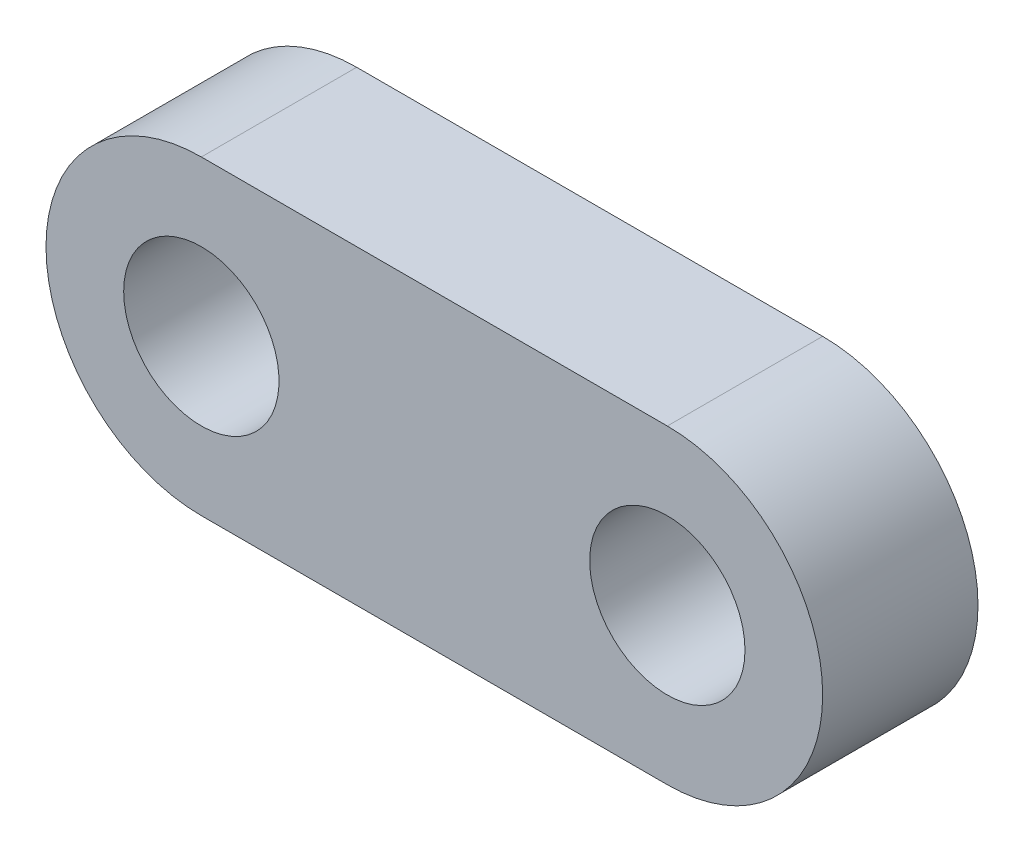
SolidWorks part; units mm, degrees
ref_plane "Front Plane" through (0, 0, 0) normal (0, 0, 1) x (1, 0, 0)
ref_plane "Top Plane" through (0, 0, 0) normal (0, 1, 0) x (1, 0, 0)
ref_plane "Right Plane" through (0, 0, 0) normal (1, 0, 0) x (0, 0, -1)
ref_plane "Plane4"
sketch "Sketch1" plane through (0, 0, 0) normal (0, 0, 1) x (1, 0, 0)
  line L0 (19.05, 0) -> (0, 0)
  line L2 (0, 12.7) -> (19.05, 12.7)
  arc A1 (0, 12.7) -> (0, 0) centre (0, 6.35) ccw
  circle A2 centre (0, 6.35) radius 3.175
  circle A3 centre (19.05, 6.35) radius 3.175
  circle A4 centre (19.05, 6.35) radius 6.35
  dimension "D1" = 19.05
extrude "Extrusion2" add sketch "Sketch1" along normal blind 6.35 contours A1 A3 A2 region at (5.2212, 6.35, 0)
extrude "Boss-Extrude1" add sketch "Sketch1<3>" along normal blind 6.35 contours A4
sketch "Sketch1<3>" plane through (0, 0, 0) normal (0, 0, 1) x (1, 0, 0) same geometry as "Sketch1"
extrude "Cut-Extrude1" cut sketch "Sketch1<4>" along normal blind 6.35 contours A3
sketch "Sketch1<4>" plane through (0, 0, 0) normal (0, 0, 1) x (1, 0, 0) same geometry as "Sketch1"
